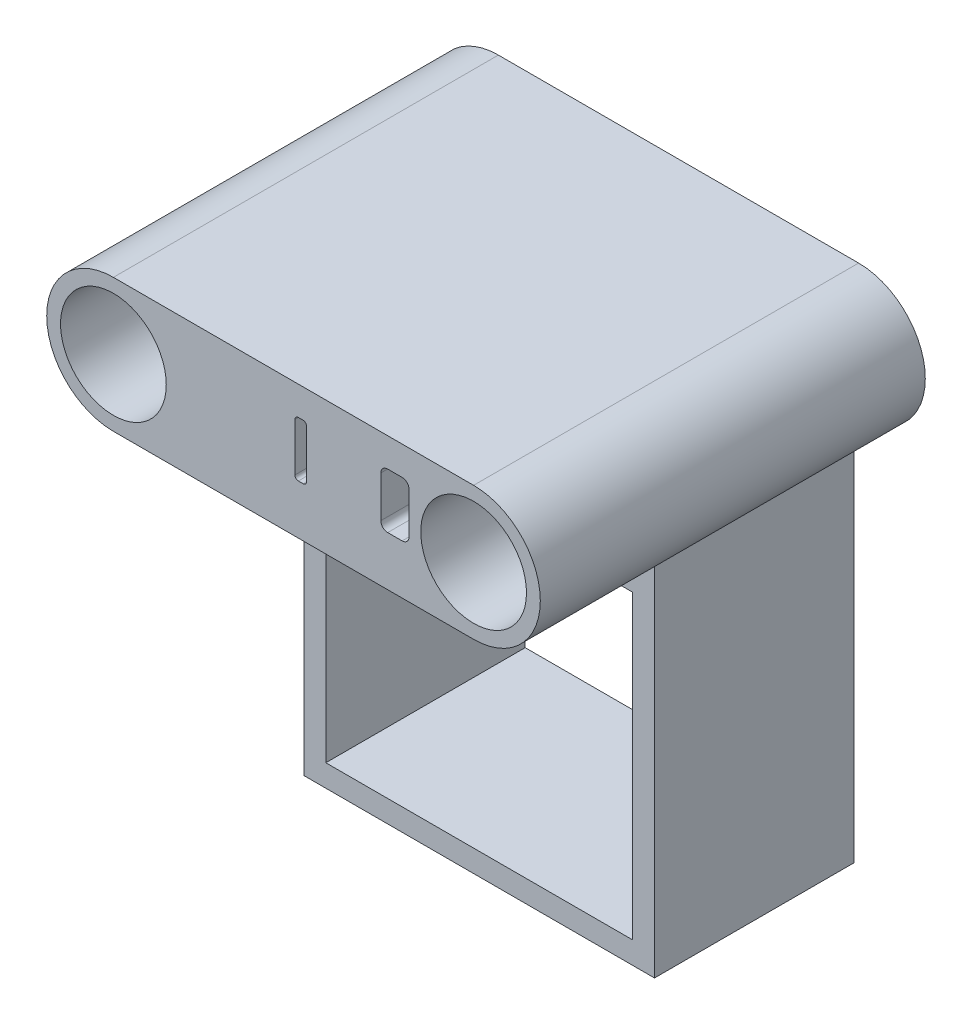
SolidWorks part; units mm, degrees
ref_plane "Front Plane" through (0, 0, 0) normal (0, 0, 1) x (1, 0, 0)
ref_plane "Top Plane" through (0, 0, 0) normal (0, 1, 0) x (1, 0, 0)
ref_plane "Right Plane" through (0, 0, 0) normal (1, 0, 0) x (0, 0, -1)
sketch "Sketch1" plane through (0, 0, 0) normal (0, 0, 1) x (1, 0, 0)
  line L0 (13.7, 5.5) -> (15.8, 5.5)
  line L1 (0.7, 5.5) -> (1.4016, 5.5)
  line L4 (15.8, -2.5) -> (13.7, -2.5)
  line L6 (12.7, -1.5) -> (12.7, 4.5)
  line L7 (0.7, -2.5) -> (1.4016, -2.5)
  line L9 (1.9016, -2) -> (1.9016, 5)
  line L13 (0.2, 5) -> (0.2, -2)
  line L87 (-26.2, 9.7) -> (26.2, 9.7)
  line L92 (16.8, 4.5) -> (16.8, -1.5)
  line L103 (-25.51, -66.21) -> (-25.51, -9.7)
  line L106 (-25.51, -66.21) -> (25.51, -66.21)
  line L108 (-25.51, -9.7) -> (-26.2, -9.7)
  line L109 (25.51, -66.21) -> (25.51, -9.7)
  line L110 (25.51, -9.7) -> (26.2, -9.7)
  circle A67 centre (26.2, 0) radius 7.69
  circle A68 centre (-26.2, 0) radius 7.69
  arc A70 (13.7, 5.5) -> (12.7, 4.5) centre (13.7, 4.5) ccw
  arc A71 (16.8, 4.5) -> (15.8, 5.5) centre (15.8, 4.5) ccw
  arc A73 (12.7, -1.5) -> (13.7, -2.5) centre (13.7, -1.5) ccw
  arc A76 (1.4016, -2.5) -> (1.9016, -2) centre (1.4016, -2) ccw
  arc A77 (0.2, -2) -> (0.7, -2.5) centre (0.7, -2) ccw
  arc A79 (0.7, 5.5) -> (0.2, 5) centre (0.7, 5) ccw
  arc A80 (1.9016, 5) -> (1.4016, 5.5) centre (1.4016, 5) ccw
  arc A83 (-26.2, 9.7) -> (-26.2, -9.7) centre (-26.2, 0) ccw
  arc A84 (26.2, -9.7) -> (26.2, 9.7) centre (26.2, 0) ccw
  arc A86 (15.8, -2.5) -> (16.8, -1.5) centre (15.8, -1.5) ccw
extrude "Boss-Extrude1" add sketch "Sketch1" along normal blind 56
sketch "Sketch2" plane through (0, 0, 0) normal (0, 0, 1) x (1, 0, 0)
  line L0 (13.7, 5.5) -> (15.8, 5.5)
  line L1 (0.7, 5.5) -> (1.4016, 5.5)
  line L2 (16.8, 4.5) -> (16.8, 2.3937)
  line L3 (15.8, -2.5) -> (13.7, -2.5)
  line L4 (12.7, -1.5) -> (12.7, 4.5)
  line L5 (0.7, -2.5) -> (1.4016, -2.5)
  line L6 (1.9016, -2) -> (1.9016, 5)
  line L7 (0.2, 5) -> (0.2, -2)
  line L26 (16.8, 2.3937) -> (16.8, -1.5)
  line L28 (1.8, -4.2) -> (9.3, -4.2)
  line L29 (1.8, -4.2) -> (1.8, -19.2)
  line L30 (1.8, -19.2) -> (9.3, -19.2)
  line L31 (9.3, -4.2) -> (9.3, -19.2)
  line L32 (-17.5, -9.7) -> (-10.5, -9.7)
  line L33 (-17.5, -9.7) -> (-17.5, -19.2)
  line L34 (-17.5, -19.2) -> (-10.5, -19.2)
  line L35 (-10.5, -9.7) -> (-10.5, -19.2)
  line L36 (10.5, -9.7) -> (17.5, -9.7)
  line L37 (10.5, -9.7) -> (10.5, -19.2)
  line L38 (10.5, -19.2) -> (17.5, -19.2)
  line L39 (17.5, -9.7) -> (17.5, -19.2)
  arc A0 (13.7, 5.5) -> (12.7, 4.5) centre (13.7, 4.5) ccw
  arc A1 (16.8, 4.5) -> (15.8, 5.5) centre (15.8, 4.5) ccw
  arc A3 (12.7, -1.5) -> (13.7, -2.5) centre (13.7, -1.5) ccw
  arc A4 (1.4016, -2.5) -> (1.9016, -2) centre (1.4016, -2) ccw
  arc A5 (0.2, -2) -> (0.7, -2.5) centre (0.7, -2) ccw
  arc A6 (0.7, 5.5) -> (0.2, 5) centre (0.7, 5) ccw
  arc A7 (1.9016, 5) -> (1.4016, 5.5) centre (1.4016, 5) ccw
  arc A9 (15.8, -2.5) -> (16.8, -1.5) centre (15.8, -1.5) ccw
sketch "Sketch3" plane through (0, 0, 56) normal (0, 0, 1) x (1, 0, 0)
  line L1 (-25.51, -66.21) -> (25.51, -66.21)
  line L2 (-25.51, -66.21) -> (-25.51, -9.7)
  line L3 (-25.51, -9.7) -> (25.51, -9.7)
  line L4 (25.51, -66.21) -> (25.51, -9.7)
extrude "Cut-Extrude1" cut sketch "Sketch3" against normal offset from surface (27 mm away) 29 up to face at (1.0508, 1.5, 0)
sketch "Sketch4" plane through (0, 0, 0) normal (0, 0, 1) x (1, 0, 0)
  line L0 (-22.3, -19.2) -> (-22.3, -63)
  line L1 (-22.3, -63) -> (22.3, -63)
  line L2 (22.3, -19.2) -> (22.3, -63)
  line L4 (-22.3, -19.2) -> (-9, -19.2)
  line L5 (-9, -6.7) -> (-9, -19.2)
  line L6 (-9, -6.7) -> (9, -6.7)
  line L7 (9, -6.7) -> (9, -19.2)
  line L8 (9, -19.2) -> (22.3, -19.2)
extrude "Cut-Extrude2" cut sketch "Sketch4" along normal up to surface (29 mm away) up to face at (0, -37.955, 29)
sketch "Sketch5" plane through (0, 0, 0) normal (0, 0, 1) x (1, 0, 0)
  line L1 (-35.9, 9.7) -> (35.9, 9.7)
  line L2 (-35.9, 9.7) -> (-35.9, -9.7)
  line L3 (-35.9, -9.7) -> (35.9, -9.7)
  line L4 (35.9, 9.7) -> (35.9, -9.7)
